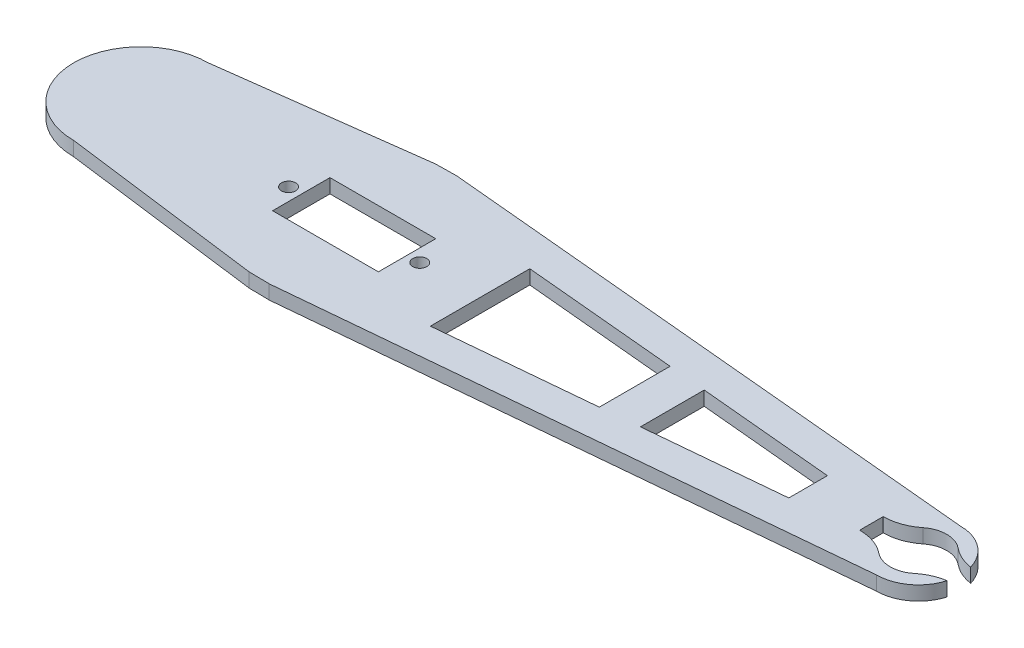
SolidWorks part; units mm, degrees
ref_plane "Front Plane" through (0, 0, 0) normal (0, 0, 1) x (1, 0, 0)
ref_plane "Top Plane" through (0, 0, 0) normal (0, 1, 0) x (1, 0, 0)
ref_plane "Right Plane" through (0, 0, 0) normal (1, 0, 0) x (0, 0, -1)
other "Center of Mass"
sketch "Sketch1" plane through (0, 0, 0) normal (0, 1, 0) x (1, 0, 0)
  line L1 (1.8468, 19.9146) -> (120, 8.9578)
  line L7 (-2.5659, -19.8347) -> (1.8468, -19.9146)
  line L8 (-11.25, 6.1) -> (11.25, 6.1)
  line L9 (-11.25, 6.1) -> (-11.25, -6.1)
  line L10 (-11.25, -6.1) -> (11.25, -6.1)
  line L11 (11.25, 6.1) -> (11.25, -6.1)
  line L12 (-11.25, 6.1) -> (11.25, -6.1) construction
  line L13 (-11.25, -6.1) -> (11.25, 6.1) construction
  line L14 (120, -8.9578) -> (1.8468, -19.9146)
  line L15 (-45.3435, 14.3009) -> (-2.5659, 19.8347)
  line L16 (-45.3435, -14.3009) -> (-2.5659, -19.8347)
  line L17 (-2.5659, 19.8347) -> (1.8468, 19.9146)
  line L18 (96.5292, 4.1043) -> (67.6603, 6.7814)
  line L19 (96.5292, -4.1043) -> (67.6603, -6.7814)
  line L20 (96.5292, 4.1043) -> (96.5292, -4.1043)
  line L21 (67.6603, 6.7814) -> (67.6603, -6.7814)
  line L22 (59.6591, 7.5234) -> (26.7796, 10.5724)
  line L23 (26.7796, 10.5724) -> (26.7796, -10.5724)
  line L24 (26.7796, -10.5724) -> (59.6591, -7.5234)
  line L25 (59.6591, -7.5234) -> (59.6591, 7.5234)
  circle A5 centre (13.95, 0) radius 1.5
  circle A6 centre (-13.95, 0) radius 1.5
  circle A7 centre (0, 0) radius 20 construction
  circle A8 centre (120, 0) radius 8.9578 construction
  arc A9 (120, 8.9578) -> (120, -8.9578) centre (120, 0) cw
  circle A10 centre (-45.3435, 0) radius 14.3009 construction
  arc A11 (-45.3435, 14.3009) -> (-45.3435, -14.3009) centre (-45.3435, 0) ccw
  circle A12 centre (120, 0) radius 6
  dimension "D5" = 3
  dimension "D6" = 3
  dimension "D7" = 40
  dimension "D13" = 12
  dimension "D14" = 2.9578
  dimension "D1" = 22.5
  dimension "D2" = 12.2
  dimension "D3" = 2.7
  dimension "D4" = 2.7
  dimension "D8" = 120
  dimension "D9" = 7
  dimension "D10" = 7
  dimension "D11" = 7
  dimension "D12" = 7
extrude "Boss-Extrude1" add sketch "Sketch1" along normal blind 3
sketch "Sketch3" plane through (0, 3, 0) normal (0, 1, 0) x (1, 0, 0)
  line L1 (130, 2.5) -> (110, 2.5)
  line L2 (130, 2.5) -> (130, -2.5)
  line L3 (130, -2.5) -> (110, -2.5)
  line L4 (110, 2.5) -> (110, -2.5)
  line L5 (130, 2.5) -> (110, -2.5) construction
  line L6 (130, -2.5) -> (110, 2.5) construction
  point P0 (120, 0)
  dimension "D1" = 5
  dimension "D2" = 20
extrude "Cut-Extrude1" cut sketch "Sketch3" against normal through all
fillet "Fillet1" radius 10 4 edges at (125.4544, 1.5, -2.5) (125.4544, 1.5, 2.5) (114.5456, 1.5, 2.5) (114.5456, 1.5, -2.5)
